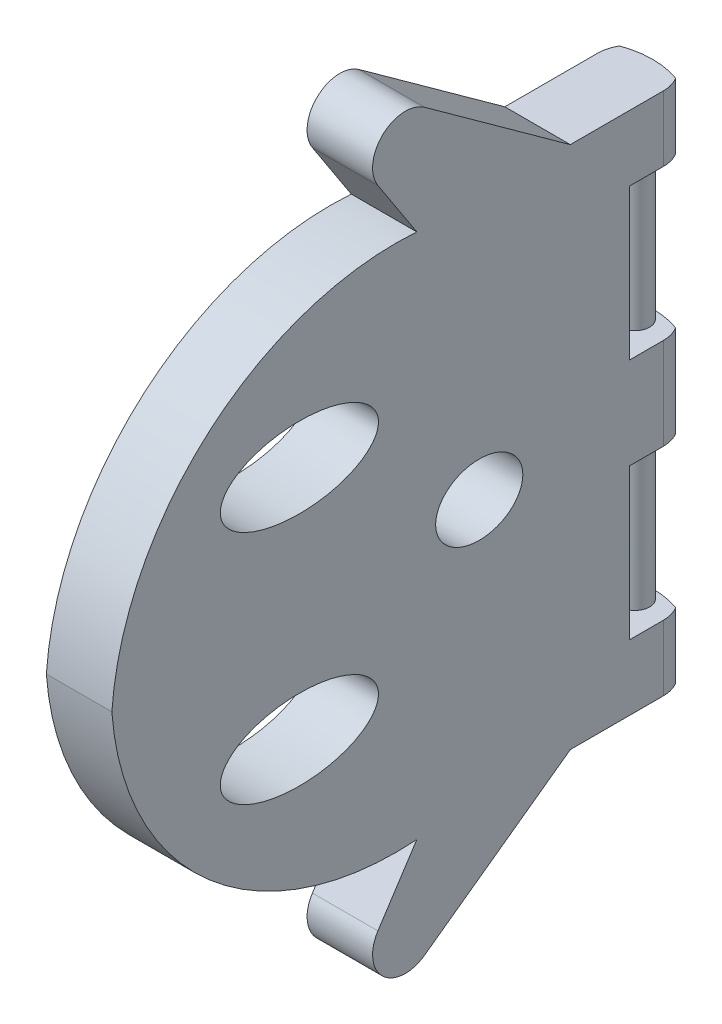
SolidWorks part; units mm, degrees
ref_plane "Alzado" through (0, 0, 0) normal (1, 0, 0) x (0, 1, 0)
ref_plane "Planta" through (0, 0, 0) normal (0, 0, 1) x (0, 1, 0)
ref_plane "Vista lateral" through (0, 0, 0) normal (0, 1, 0) x (-1, 0, 0)
sketch "Croquis1" plane through (0, 0, 0) normal (1, 0, 0) x (0, 1, 0)
  line L0 (-20, 0) -> (20, 0) construction
  line L9 (0, 0) -> (0, 35) construction
  line L12 (20.0847, 11.7175) -> (24.6416, 14.6892)
  line L14 (28.0344, 11.132) -> (20, 0)
  line L16 (-28.0344, 11.132) -> (-20, 0)
  line L17 (-20.0847, 11.7175) -> (-24.6416, 14.6892)
  line L18 (-20, 0) -> (-20, -10)
  line L19 (-20, -10) -> (-15, -10)
  line L20 (20, -10) -> (20, 0)
  line L21 (-20, -10) -> (-15, -10) construction
  line L23 (20, -10) -> (15, -10) construction
  line L25 (-3.5, -10) -> (3.5, -10) construction
  line L26 (-15, -4.5) -> (-3.5, -4.5)
  line L27 (-15, -10) -> (-15, -4.5) construction
  line L28 (3.5, -4.5) -> (15, -4.5)
  line L29 (-3.5, -4.5) -> (-3.5, -10)
  line L30 (3.5, -10) -> (3.5, -4.5)
  line L31 (15, -4.5) -> (15, -10)
  line L32 (-15, -4.5) -> (-15, -10)
  line L33 (-3.5, -10) -> (3.5, -10)
  line L34 (15, -10) -> (20, -10)
  arc A0 (0, 35) -> (20.0847, 11.7175) centre (-1.5943, 13.3204) cw
  arc A1 (24.6416, 14.6892) -> (28.0344, 11.132) centre (26.0072, 12.5951) cw
  arc A2 (-24.6416, 14.6892) -> (-28.0344, 11.132) centre (-26.0072, 12.5951) ccw
  arc A3 (0, 35) -> (-20.0847, 11.7175) centre (1.5943, 13.3204) ccw
  ellipse E0 centre (-8.9972, 20.6852) end of major axis (-8.9972, 26.7218) minor radius 3.0705
  ellipse E1 centre (0, 6.9531) end of major axis (0, 3.6267) minor radius 2.6879
  ellipse E2 centre (8.9972, 20.6852) end of major axis (8.9972, 26.7218) minor radius 3.0705
  point P3 (0, 0)
  dimension "D2" = 35
  dimension "D3" = 2.5
  dimension "D5" = 5
  dimension "D4" = 10
  dimension "D6" = 5.5
  dimension "D1" = 40
  dimension "D7" = 5.5
  dimension "D8" = 11.5
  dimension "D9" = 11.5
extrude "Saliente-Extruir2" add sketch "Croquis1" along normal blind 5
sketch "Croquis3" plane through (0, 3.5, 0) normal (0, 1, 0) x (-1, 0, 0)
  line L1 (-5, -4.5) -> (0, -4.5) construction
  line L3 (0, -10) -> (0, -4.5) construction
  circle A1 centre (-2.5, -7.45) radius 1.1
  dimension "D2" = 2.2
  dimension "D1" = 2.95
  dimension "D3" = 2.5
sketch "Croquis6" plane through (0, -3.5, 0) normal (0, -1, 0) x (1, 0, 0)
  line L1 (5, -4.5) -> (5, -10) construction
  line L3 (5, -4.5) -> (0, -4.5) construction
  circle A0 centre (2.5, -7.45) radius 1.1
  dimension "D3" = 2.2
  dimension "D1" = 2.95
  dimension "D2" = 2.5
sketch "Croquis7" plane through (0, 0, 0) normal (1, 0, 0) x (0, 1, 0)
  line L1 (-21.9915, -10.4921) -> (20.699, -10.4921)
  line L2 (-21.9915, -10.4921) -> (-21.9915, -9.602)
  line L3 (-21.9915, -9.602) -> (20.699, -9.602)
  line L4 (20.699, -10.4921) -> (20.699, -9.602)
extrude "Cortar-Extruir1" cut sketch "Croquis7" along normal blind 10
fillet "Redondeo1" radius 2.5 6 edges at (0, 17.5, -9.602) (5, 17.5, -9.602) (0, 0, -9.602) (5, 0, -9.602) (0, -17.5, -9.602) (5, -17.5, -9.602)
extrude "Saliente-Extruir3" add sketch "Croquis3" along normal blind 11.5
extrude "Saliente-Extruir4" add sketch "Croquis6" along normal blind 11.5 contours A0
sketch "Croquis8" plane through (0, 20, 0) normal (0, 1, 0) x (-1, 0, 0)
  arc A0 (-6.8862, -6.9941) -> (1.8636, -6.9941) centre (-2.5113, -2.5342) ccw
extrude "Cortar-Extruir2" cut sketch "Croquis8" against normal through all and the other way through all flip side to cut
